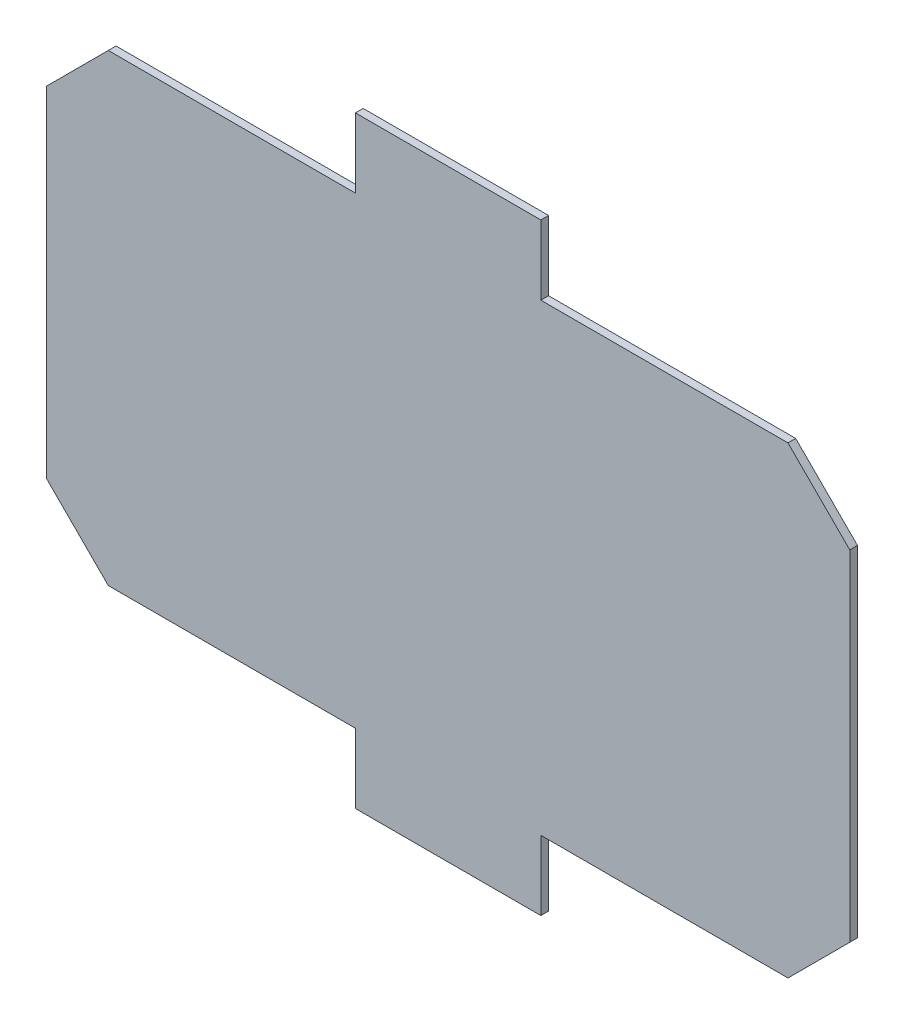
SolidWorks part; units mm, degrees
ref_plane "Front Plane" through (0, 0, 0) normal (0, 0, 1) x (1, 0, 0)
ref_plane "Top Plane" through (0, 0, 0) normal (0, 1, 0) x (1, 0, 0)
ref_plane "Right Plane" through (0, 0, 0) normal (1, 0, 0) x (0, 0, -1)
sketch "Sketch1" plane through (0, 0, 0) normal (0, 0, 1) x (1, 0, 0)
  line L0 (-100, 395) -> (-75, 395) construction
  line L1 (-60, -45) -> (60, -45)
  line L2 (-60, -45) -> (-60, 395)
  line L3 (-60, 395) -> (60, 395)
  line L4 (60, -45) -> (60, 395)
  line L5 (-60, -45) -> (60, 395) construction
  line L6 (-60, 395) -> (60, -45) construction
  line L7 (100, -45) -> (75, -45) construction
  line L8 (60, 392.6) -> (60, 325) construction
  line L9 (-60, 392.6) -> (-60, 325) construction
  line L11 (-260, 25) -> (260, 25)
  line L12 (-260, 25) -> (-260, 325)
  line L13 (-260, 325) -> (260, 325)
  line L14 (260, 25) -> (260, 325)
  line L15 (-260, 25) -> (260, 325) construction
  line L16 (-260, 325) -> (260, 25) construction
  point P0 (0, 175)
  point P13 (0, 175)
  dimension "D1" = 520
  dimension "D2" = 300
extrude "Boss-Extrude1" add sketch "Sketch1" along normal blind 5 contours L2 L13 L4 L3 | L13 L12 L11 L2 | L13 L2 L11 L4 | L11 L14 L13 L4 | L11 L2 L1 L4 region at (0, -10, 0) region at (-160, 175, 0) region at (0, 175, 0) region at (160, 175, 0) region at (0, 360, 0)
chamfer "Chamfer1" distance 40 angle 45 4 edges at (260, 25, 2.5) (260, 325, 2.5) (-260, 325, 2.5) (-260, 25, 2.5)
sketch "Sketch2" plane through (0, 0, 5) normal (0, 0, 1) x (1, 0, 0)
  line L0 (-260, 175) -> (260, 175) construction
  line L1 (-260, 65) -> (-260, 285) construction
  line L2 (260, 65) -> (260, 285) construction
  line L3 (60, 325) -> (60, 395) construction
  line L4 (-60, 395) -> (60, 395)
  line L5 (-60, 395) -> (-60, 370)
  line L6 (-60, 370) -> (60, 370)
  line L7 (60, 395) -> (60, 370)
  line L8 (-69, 370) -> (69, 370) construction
  line L9 (60, -45) -> (60, -20)
  line L10 (-60, -20) -> (60, -20)
  line L11 (-60, -45) -> (-60, -20)
  line L12 (-60, -45) -> (60, -45)
extrude "Cut-Extrude1" cut sketch "Sketch2" against normal blind 25
